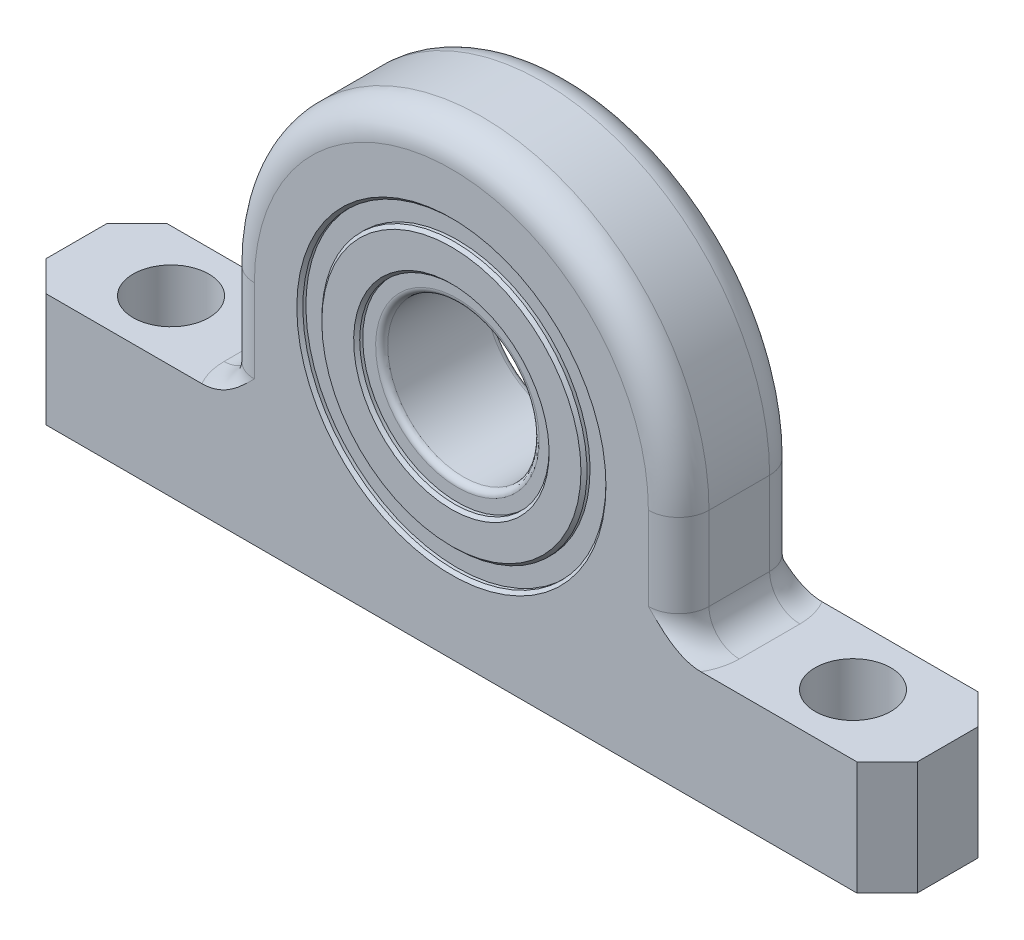
SolidWorks part; units mm, degrees
ref_plane "Front Plane" through (0, 0, 0) normal (0, 0, 1) x (1, 0, 0)
ref_plane "Top Plane" through (0, 0, 0) normal (0, 1, 0) x (1, 0, 0)
ref_plane "Right Plane" through (0, 0, 0) normal (1, 0, 0) x (0, 0, -1)
sketch "Sketch1" plane through (0, 0, 0) normal (0, 0, 1) x (1, 0, 0)
  line L0 (9.525, 0) -> (9.525, -4.7625)
  line L1 (9.525, -4.7625) -> (18.2562, -4.7625)
  line L2 (18.2562, -4.7625) -> (18.2562, -9.525)
  line L3 (18.2562, -9.525) -> (-18.2562, -9.525)
  line L4 (-18.2562, -9.525) -> (-18.2563, -4.7625)
  line L5 (-18.2563, -4.7625) -> (-9.525, -4.7625)
  line L6 (-9.525, -4.7625) -> (-9.525, 0)
  circle A0 centre (0, 0) radius 3.175
  arc A1 (9.525, 0) -> (-9.525, 0) centre (0, 0) ccw
  circle A2 centre (0, 0) radius 6.35
  dimension "D1" = 12.7
sketch "Sketch2" plane through (0, 0, 0) normal (0, 1, 0) x (1, 0, 0)
  line L0 (0, 2.54) -> (0, -2.54) construction
  line L1 (-14.2875, 0) -> (14.2875, 0) construction
  circle A0 centre (14.2875, 0) radius 1.5875
  circle A1 centre (-14.2875, 0) radius 1.5875
sketch "Sketch3" plane through (0, 0, 0) normal (0, 0, 1) x (1, 0, 0)
  line L0 (9.525, 0) -> (9.525, -4.7625) construction
  line L1 (18.2562, -4.7625) -> (18.2562, -9.525) construction
  line L2 (9.525, -4.7625) -> (18.2562, -4.7625) construction
  line L3 (18.2562, -9.525) -> (-18.2562, -9.525) construction
  line L4 (-18.2562, -9.525) -> (-18.2563, -4.7625) construction
  line L5 (-18.2563, -4.7625) -> (-9.525, -4.7625) construction
  line L6 (-9.525, -4.7625) -> (-9.525, 0) construction
  line L7 (9.525, 0) -> (9.525, -4.7625)
  line L8 (18.2562, -4.7625) -> (18.2562, -9.525)
  line L9 (9.525, -4.7625) -> (18.2562, -4.7625)
  line L10 (18.2562, -9.525) -> (-18.2562, -9.525)
  line L11 (-18.2562, -9.525) -> (-18.2563, -4.7625)
  line L12 (-18.2563, -4.7625) -> (-9.525, -4.7625)
  line L13 (-9.525, -4.7625) -> (-9.525, 0)
  arc A0 (9.525, 0) -> (-9.525, 0) centre (0, 0) ccw construction
  circle A1 centre (0, 0) radius 6.35 construction
  arc A2 (9.525, 0) -> (-9.525, 0) centre (0, 0) ccw
  circle A3 centre (0, 0) radius 6.35
extrude "Extrude1" add sketch "Sketch3" along normal up to vertex (2.54 mm away) and the other way up to vertex (2.54 mm away) up to point (0, 0, 2.54) other way up to point (0, 0, -2.54)
sketch "Sketch4" plane through (0, -4.7625, 0) normal (0, 1, 0) x (1, 0, 0)
  line L0 (-18.2563, 2.54) -> (-18.2562, 1.27)
  line L1 (-18.2563, -2.54) -> (-18.2563, 2.54) construction
  line L2 (-18.2562, 1.27) -> (-16.9863, 2.54)
  line L3 (-9.525, 2.54) -> (-18.2563, 2.54) construction
  line L4 (-16.9863, 2.54) -> (-18.2563, 2.54)
  line L5 (0, 0) -> (0, 2.54) construction
  line L6 (0, 0) -> (-14.2875, 0) construction
  line L7 (16.9863, 2.54) -> (18.2563, 2.54)
  line L8 (18.2562, 1.27) -> (16.9863, 2.54)
  line L9 (18.2563, 2.54) -> (18.2562, 1.27)
  line L10 (18.2563, -2.54) -> (18.2562, -1.27)
  line L11 (18.2562, -1.27) -> (16.9863, -2.54)
  line L12 (16.9863, -2.54) -> (18.2563, -2.54)
  line L13 (-16.9863, -2.54) -> (-18.2563, -2.54)
  line L14 (-18.2562, -1.27) -> (-16.9863, -2.54)
  line L15 (-18.2563, -2.54) -> (-18.2562, -1.27)
  circle A0 centre (-14.2875, 0) radius 1.5875 construction
  circle A1 centre (14.2875, 0) radius 1.5875 construction
  circle A2 centre (-14.2875, 0) radius 1.5875
  circle A3 centre (14.2875, 0) radius 1.5875
  dimension "D1" = 45
  dimension "D2" = 1.27
extrude "Cut-Extrude1" cut sketch "Sketch4" against normal through all
fillet "Fillet1" radius 1.27 6 edges at (9.525, -2.3812, -2.54) (-9.525, -2.3812, -2.54) (9.525, -2.3812, 2.54) (-9.525, -2.3812, 2.54) (0, 9.525, -2.54) (0, 9.525, 2.54)
fillet "Fillet2" radius 1.27 6 edges at (-9.153, -4.7625, 2.168) (-9.153, -4.7625, -2.168) (9.153, -4.7625, 2.168) (9.153, -4.7625, -2.168) (-9.525, -4.7625, 0) (9.525, -4.7625, 0)
chamfer "Chamfer1" distance 0.127 angle 45 2 edges at (6.35, 0, -2.54) (6.35, 0, 2.54)
sketch "Sketch5" plane through (0, 0, 0) normal (1, 0, 0) x (0, 0, -1)
  line L0 (0, 0) -> (0, 6.35) construction
  line L1 (0, 6.35) -> (0, -6.35) construction
  line L2 (0, 3.175) -> (0, -3.175) construction
  line L3 (-2.286, 6.35) -> (-2.286, 5.5562)
  line L4 (-2.286, 5.5562) -> (-2.54, 5.5563)
  line L5 (-2.54, 5.5563) -> (-2.54, 3.9688)
  line L6 (-2.54, 3.9688) -> (-2.286, 3.9688)
  line L7 (-2.286, 3.9688) -> (-2.286, 3.175)
  line L8 (-2.286, 3.175) -> (2.286, 3.175)
  line L9 (0, 3.175) -> (0, 6.35) construction
  line L10 (-2.286, 6.35) -> (2.286, 6.35)
  line L11 (-2.54, 8.255) -> (-2.54, 0) construction
  line L12 (2.286, 3.9688) -> (2.286, 3.175)
  line L13 (2.54, 3.9688) -> (2.286, 3.9688)
  line L14 (2.54, 5.5563) -> (2.54, 3.9688)
  line L15 (2.286, 5.5562) -> (2.54, 5.5563)
  line L16 (2.286, 6.35) -> (2.286, 5.5562)
  line L17 (0, 0) -> (-2.54, 0) construction
  point P6 (0, 3.175)
  dimension "D2" = 3.175
  dimension "D3" = 1.5875
revolve "Revolve1" add sketch "Sketch5" angle 360 about L17
fillet "Fillet3" radius 0.254 2 edges at (0, 3.175, 2.286) (0, 3.175, -2.286)
chamfer "Chamfer2" distance 0.127 angle 45 4 edges at (0, 3.9688, -2.54) (0, 5.5563, -2.54) (0, 5.5563, 2.54) (0, 3.9688, 2.54)
equation "\"D1@Sketch1\" = \"shaft dia@Sketch1\"*2."
equation "\"D2@Sketch4\" = \"E@Sketch2\"/4"
equation "\"D1@Fillet1\" = \"D2@Sketch4\""
equation "\"D1@Fillet2\" = \"D1@Fillet1\""
equation "\"D3@Sketch5\" = \"D2@Sketch5\"/2"
